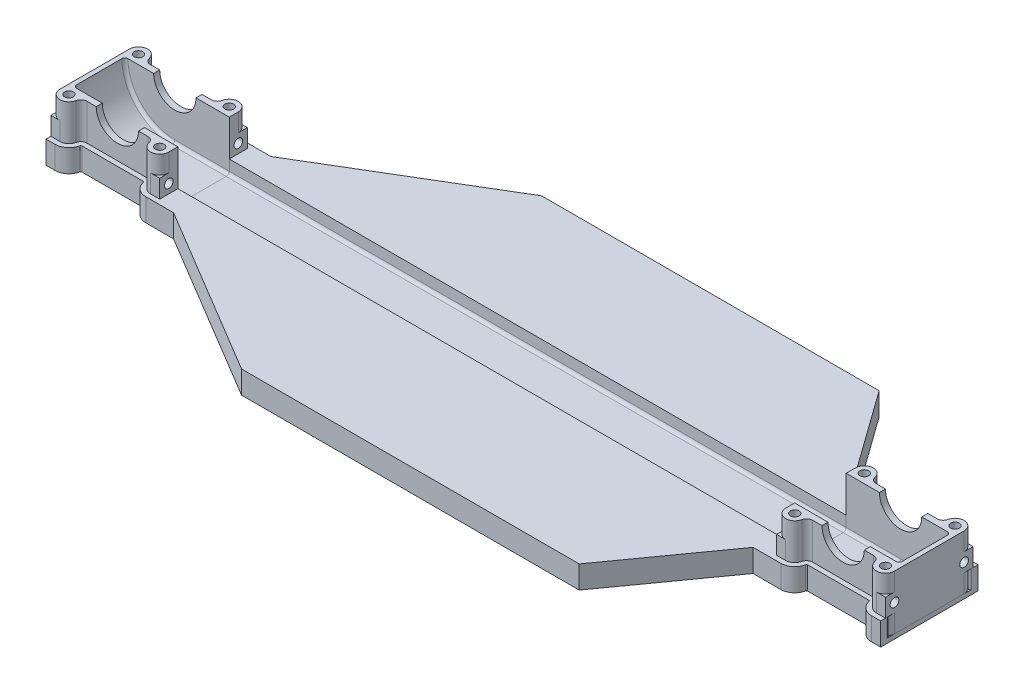
SolidWorks part; units mm, degrees
note: The reader was unsure of these and kept them because the rebuilt part matched: shared geometry of "Sketch1<3>", "Sketch1<4>", "Sketch2<3>", "Sketch3<4>", "Sketch3<5>", "Sketch7<2>", "Sketch7<3>", "Sketch7<4>".
material "6061-T6 (SS)"
ref_plane "Front" through (0, 0, 0) normal (0, 0, 1) x (1, 0, 0)
ref_plane "Top" through (0, 0, 0) normal (0, 1, 0) x (1, 0, 0)
ref_plane "Right" through (0, 0, 0) normal (1, 0, 0) x (0, 0, -1)
sketch "Sketch1" plane through (0, 0, 0) normal (0, 0, 1) x (1, 0, 0)
  line L0 (-28.575, 0) -> (28.575, 0)
  line L1 (-28.575, 0) -> (-28.575, -28.575)
  line L2 (-28.575, -28.575) -> (28.575, -28.575)
  line L3 (28.575, -28.575) -> (28.575, 0)
  line L4 (0, -26.1937) -> (28.575, -26.1937)
  arc A0 (-26.1937, 0) -> (26.1937, 0) centre (0, 0) ccw
  arc A1 (-11.1125, 0) -> (11.1125, 0) centre (0, 0) ccw
  arc A2 (-28.575, 0) -> (28.575, 0) centre (0, 0) ccw
  circle A3 centre (0, 0) radius 28.575 construction
  circle A4 centre (0, 0) radius 26.1937 construction
  dimension "D1" = 52.3875
  dimension "D2" = 22.225
  dimension "D3" = 2.3813
extrude "Boss-Extrude1" add sketch "Sketch1" along normal mid plane 26.9875 contours L0 A2 L4 A0 | A2 L2 L3 L4 | A2 L1 L2
extrude "Boss-Extrude2" add sketch "Sketch1<3>" against normal blind 3.175 from surface contours A2 L1 L2 | L0 A2 L4 A0 | A2 L2 L3 L4 | A2 L4 L3 | L4 A2 L0 A0 | A1 L0 A0
sketch "Sketch1<3>" plane through (0, 0, 0) normal (0, 0, 1) x (1, 0, 0) same geometry as "Sketch1"
extrude "Boss-Extrude3" add sketch "Sketch1<4>" along normal blind 3.175 from surface at 13.4938 contours A2 L1 L2 | L0 A2 L4 A0 | A2 L2 L3 L4 | A2 L4 L3 | L4 A2 L0 A0 | A1 L0 A0 starting at face at (-5.2698, -19.1604, 13.4937)
sketch "Sketch1<4>" plane through (0, 0, 0) normal (0, 0, 1) x (1, 0, 0) same geometry as "Sketch1"
sketch "Sketch2" plane through (0, -28.575, 0) normal (0, -1, 0) x (1, 0, 0)
  line L4 (-28.575, 16.6687) -> (-28.575, -16.6687)
  line L5 (-28.575, 18.2562) -> (-28.575, -18.2563)
  line L6 (-19.05, -18.2563) -> (-19.05, 18.2562)
  line L7 (19.05, 18.2562) -> (19.05, -18.2563)
  line L8 (28.575, -18.2563) -> (28.575, 18.2563)
  line L9 (-28.575, 16.6687) -> (-28.575, -16.6687)
  line L10 (-28.575, -16.6687) -> (28.575, -16.6687)
  line L12 (28.575, 16.6687) -> (-28.575, 16.6687)
  line L16 (28.575, 16.6687) -> (-28.575, 16.6687)
  line L17 (11.1125, -13.4937) -> (-11.1125, -13.4937) construction
  line L18 (-11.1125, 13.4937) -> (11.1125, 13.4937) construction
  line L19 (11.1125, -13.4937) -> (-11.1125, -13.4937)
  line L20 (-11.1125, 13.4937) -> (11.1125, 13.4937)
  line L21 (28.575, -16.6687) -> (28.575, 16.6687)
  line L22 (28.575, -16.6687) -> (28.575, 16.6687)
  line L37 (-28.575, -16.6687) -> (28.575, -16.6687)
  circle A0 centre (-23.8125, 18.2562) radius 4.7625
  circle A1 centre (23.8125, 18.2562) radius 4.7625
  circle A2 centre (-23.8125, -18.2563) radius 4.7625
  circle A3 centre (23.8125, -18.2563) radius 4.7625
  circle A4 centre (-23.8125, 18.2562) radius 2.286
  circle A5 centre (23.8125, 18.2562) radius 2.286
  circle A6 centre (23.8125, -18.2563) radius 2.286
  circle A7 centre (-23.8125, -18.2563) radius 2.286
  line M6 (-28.575, -16.6687) -> (28.575, -16.6687)
  line M8 (28.575, 16.6687) -> (-28.575, 16.6687)
  dimension "D1" = 9.525
  dimension "D5" = 4.572
  dimension "D2" = 0
extrude "Boss-Extrude4" add sketch "Sketch2" against normal up to surface (28.575 mm away) contours A0 L5 M8 | A1 L8 M8 | A3 L8 M6 | A2 L5 M6
fillet "Fillet3" radius 1.5875 4 edges at (-18.5218, -18.5218, -13.4937) (-18.5218, -18.5218, 13.4937) (14.2875, -26.1937, -13.4937) (14.2875, -26.1937, 13.4937)
extrude "Cut-Extrude1" cut sketch "Sketch2<3>" against normal through all both and the other way through all contours A4 | A5 | A6 | A7
sketch "Sketch2<3>" plane through (0, -28.575, 0) normal (0, -1, 0) x (1, 0, 0) same geometry as "Sketch2"
fillet "Fillet7" radius 3.175 4 edges at (19.3224, -14.2875, -16.6687) (-19.3224, -14.2875, -16.6687) (19.3224, -14.2875, 16.6687) (-19.3224, -14.2875, 16.6687)
ref_plane "Plane1" through (190.5, 0, 0) normal (1, 0, 0) x (0, 0, -1)
mirror "Mirror5" about plane through (190.5, 0, 0) normal (1, 0, 0) of bodies 106
sketch "Sketch3" plane through (0, -28.575, 0) normal (0, -1, 0) x (1, 0, 0)
  line L0 (352.425, 18.2563) -> (352.425, -18.2563) construction
  line L1 (364.9646, -16.6687) -> (397.0354, -16.6687) construction
  line L2 (409.575, -18.2563) -> (409.575, 18.2562) construction
  line L3 (397.0354, 16.6687) -> (364.9646, 16.6687) construction
  line L4 (16.0354, 16.6687) -> (-16.0354, 16.6687) construction
  line L5 (-28.575, 18.2562) -> (-28.575, -18.2563) construction
  line L6 (-16.0354, -16.6687) -> (16.0354, -16.6687) construction
  line L7 (28.575, -18.2563) -> (28.575, 18.2563) construction
  line L8 (352.425, 18.2563) -> (352.425, -18.2563)
  line L9 (364.9646, -16.6687) -> (397.0354, -16.6687)
  line L10 (409.575, -18.2563) -> (409.575, 18.2562)
  line L11 (397.0354, 16.6687) -> (364.9646, 16.6687)
  line L12 (16.0354, 16.6687) -> (-16.0354, 16.6687)
  line L13 (-28.575, 18.2562) -> (-28.575, -18.2563)
  line L14 (-16.0354, -16.6687) -> (16.0354, -16.6687)
  line L15 (28.575, -18.2563) -> (28.575, 18.2563)
  line L16 (-24.3902, 22.9836) -> (-24.1024, 23.0188) construction
  line L17 (-24.1024, 23.0188) -> (39.0844, 23.0188) construction
  line L18 (39.0844, 23.0188) -> (127.9844, 76.2) construction
  line L19 (127.9844, 76.2) -> (303.2125, 76.2) construction
  line L20 (303.2125, 76.2) -> (341.3125, 23.0188) construction
  line L21 (341.3125, 23.0188) -> (392.1125, 23.0188) construction
  line L22 (342.6174, -25.5588) -> (394.6083, -25.5588) construction
  line L23 (-28.575, 0) -> (409.575, 0) construction
  line L24 (342.6174, 25.5588) -> (392.2671, 25.5588) construction
  line L25 (157.1625, 15.875) -> (300.0375, 15.875)
  line L26 (157.1625, 15.875) -> (157.1625, 69.85)
  line L27 (157.1625, 69.85) -> (300.0375, 69.85)
  line L28 (300.0375, 15.875) -> (300.0375, 69.85)
  line L29 (157.1625, -15.875) -> (300.0375, -15.875)
  line L30 (157.1625, -15.875) -> (157.1625, -69.85)
  line L31 (157.1625, -69.85) -> (300.0375, -69.85)
  line L32 (300.0375, -15.875) -> (300.0375, -69.85)
  line L33 (341.3125, -23.0188) -> (392.1125, -23.0188) construction
  line L34 (303.2125, -76.2) -> (341.3125, -23.0188) construction
  line L35 (127.9844, -76.2) -> (303.2125, -76.2) construction
  line L36 (39.0844, -23.0188) -> (127.9844, -76.2) construction
  line L37 (-24.1024, -23.0188) -> (39.0844, -23.0188) construction
  line L38 (-24.3902, -22.9836) -> (-24.1024, -23.0188) construction
  line L39 (-24.2571, 25.5588) -> (38.3826, 25.5588) construction
  line L40 (-23.8125, 25.5587) -> (38.3826, 25.5588)
  line L41 (38.3826, 25.5588) -> (127.2826, 78.74)
  line L42 (127.2826, 78.74) -> (304.5174, 78.74)
  line L43 (304.5174, 78.74) -> (342.6174, 25.5588)
  line L44 (342.6174, 25.5588) -> (404.8125, 25.5587)
  line L45 (-24.2571, -25.5588) -> (38.3826, -25.5588) construction
  line L46 (-31.115, 18.2562) -> (-31.115, 25.5588)
  line L47 (-23.8125, -25.5588) -> (38.3826, -25.5588)
  line L48 (38.3826, -25.5588) -> (127.2826, -78.74)
  line L49 (127.2826, -78.74) -> (304.5174, -78.74)
  line L50 (304.5174, -78.74) -> (342.6174, -25.5588)
  line L51 (342.6174, -25.5588) -> (404.8125, -25.5588)
  line L52 (-31.115, 25.5588) -> (-23.8125, 25.5587)
  line L53 (31.115, -18.2563) -> (31.115, 18.2563)
  line L54 (16.0354, 19.2087) -> (-16.0354, 19.2087)
  line L55 (-31.115, 18.2562) -> (-31.115, -18.2563)
  line L56 (-16.0354, -19.2087) -> (16.0354, -19.2087)
  line L57 (349.885, 18.2563) -> (349.885, -18.2563)
  line L58 (364.9646, -19.2087) -> (397.0354, -19.2087)
  line L59 (412.115, -18.2563) -> (412.115, 18.2562)
  line L60 (397.0354, 19.2087) -> (364.9646, 19.2087)
  line L61 (352.425, 13.4937) -> (369.8875, 13.4937) construction
  line L62 (369.8875, -13.4937) -> (352.425, -13.4937) construction
  line L63 (28.575, 13.4937) -> (11.1125, 13.4937) construction
  line L64 (11.1125, -13.4937) -> (28.575, -13.4937) construction
  line L65 (352.425, 13.4937) -> (369.8875, 13.4937)
  line L66 (369.8875, -13.4937) -> (352.425, -13.4937)
  line L67 (28.575, 13.4937) -> (11.1125, 13.4937)
  line L68 (11.1125, -13.4937) -> (28.575, -13.4937)
  line L69 (-31.115, -18.2563) -> (-31.115, -25.5588)
  line L70 (11.1125, 13.4937) -> (369.8875, 13.4937)
  line L71 (11.1125, 13.4937) -> (11.1125, -13.4937)
  line L72 (11.1125, -13.4937) -> (369.8875, -13.4937)
  line L73 (369.8875, 13.4937) -> (369.8875, -13.4937)
  line L74 (392.1125, 23.0188) -> (405.3902, 21.3961) construction
  line L75 (392.1125, -23.0188) -> (392.1166, -22.7857) construction
  line L76 (394.6083, -25.5588) -> (394.6562, -22.8303) construction
  line L77 (392.2671, 25.5588) -> (405.6983, 23.9173) construction
  line L78 (-24.6983, -25.5048) -> (-24.2571, -25.5588) construction
  line L79 (-24.6983, 25.5048) -> (-24.2571, 25.5588) construction
  line L80 (-31.115, -25.5588) -> (-23.8125, -25.5588)
  line L81 (404.8125, 25.5587) -> (412.115, 25.5588)
  line L82 (412.115, 25.5588) -> (412.115, 18.2562)
  line L83 (412.115, -18.2563) -> (412.115, -25.5588)
  line L84 (412.115, -25.5588) -> (404.8125, -25.5588)
  arc A0 (361.8538, 19.2087) -> (352.425, 18.2563) centre (357.1875, 18.2562) ccw construction
  circle A1 centre (404.8125, 18.2562) radius 2.286
  circle A2 centre (404.8125, 18.2562) radius 2.286
  circle A3 centre (357.1875, 18.2562) radius 2.286
  circle A4 centre (357.1875, 18.2562) radius 2.286
  circle A5 centre (357.1875, -18.2563) radius 2.286
  circle A6 centre (357.1875, -18.2563) radius 2.286
  circle A7 centre (404.8125, -18.2563) radius 2.286
  circle A8 centre (404.8125, -18.2563) radius 2.286
  circle A9 centre (-23.8125, 18.2562) radius 2.286
  circle A10 centre (-23.8125, 18.2562) radius 2.286
  circle A11 centre (23.8125, 18.2562) radius 2.286
  circle A12 centre (23.8125, 18.2562) radius 2.286
  circle A13 centre (23.8125, -18.2563) radius 2.286
  circle A14 centre (23.8125, -18.2563) radius 2.286
  circle A15 centre (-23.8125, -18.2563) radius 2.286
  circle A16 centre (-23.8125, -18.2563) radius 2.286
  arc A17 (352.425, -18.2563) -> (361.8538, -19.2088) centre (357.1875, -18.2563) ccw construction
  arc A18 (364.9646, -16.6687) -> (361.8538, -19.2088) centre (364.9646, -19.8438) ccw construction
  arc A19 (400.1462, -19.2088) -> (397.0354, -16.6687) centre (397.0354, -19.8438) ccw construction
  arc A20 (400.1462, -19.2088) -> (409.575, -18.2563) centre (404.8125, -18.2563) ccw construction
  arc A21 (409.575, 18.2562) -> (400.1462, 19.2087) centre (404.8125, 18.2562) ccw construction
  arc A22 (397.0354, 16.6687) -> (400.1462, 19.2087) centre (397.0354, 19.8438) ccw construction
  arc A23 (361.8538, 19.2087) -> (364.9646, 16.6687) centre (364.9646, 19.8438) ccw construction
  arc A24 (28.575, 18.2563) -> (19.1462, 19.2087) centre (23.8125, 18.2562) ccw construction
  arc A25 (16.0354, 16.6687) -> (19.1462, 19.2087) centre (16.0354, 19.8438) ccw construction
  arc A26 (-19.1462, 19.2087) -> (-16.0354, 16.6687) centre (-16.0354, 19.8438) ccw construction
  arc A27 (-19.1462, 19.2087) -> (-28.575, 18.2562) centre (-23.8125, 18.2562) ccw construction
  arc A28 (-28.575, -18.2563) -> (-19.1462, -19.2088) centre (-23.8125, -18.2563) ccw construction
  arc A29 (-16.0354, -16.6687) -> (-19.1462, -19.2088) centre (-16.0354, -19.8438) ccw construction
  arc A30 (19.1462, -19.2088) -> (16.0354, -16.6687) centre (16.0354, -19.8438) ccw construction
  arc A31 (19.1462, -19.2088) -> (28.575, -18.2563) centre (23.8125, -18.2563) ccw construction
  arc A32 (361.8538, 19.2087) -> (352.425, 18.2563) centre (357.1875, 18.2562) ccw
  arc A33 (352.425, -18.2563) -> (361.8538, -19.2088) centre (357.1875, -18.2563) ccw
  arc A34 (364.9646, -16.6687) -> (361.8538, -19.2088) centre (364.9646, -19.8438) ccw
  arc A35 (400.1462, -19.2088) -> (397.0354, -16.6687) centre (397.0354, -19.8438) ccw
  arc A36 (400.1462, -19.2088) -> (409.575, -18.2563) centre (404.8125, -18.2563) ccw
  arc A37 (409.575, 18.2562) -> (400.1462, 19.2087) centre (404.8125, 18.2562) ccw
  arc A38 (397.0354, 16.6687) -> (400.1462, 19.2087) centre (397.0354, 19.8438) ccw
  arc A39 (361.8538, 19.2087) -> (364.9646, 16.6687) centre (364.9646, 19.8438) ccw
  arc A40 (28.575, 18.2563) -> (19.1462, 19.2087) centre (23.8125, 18.2562) ccw
  arc A41 (16.0354, 16.6687) -> (19.1462, 19.2087) centre (16.0354, 19.8438) ccw
  arc A42 (-19.1462, 19.2087) -> (-16.0354, 16.6687) centre (-16.0354, 19.8438) ccw
  arc A43 (-19.1462, 19.2087) -> (-28.575, 18.2562) centre (-23.8125, 18.2562) ccw
  arc A44 (-28.575, -18.2563) -> (-19.1462, -19.2088) centre (-23.8125, -18.2563) ccw
  arc A45 (-16.0354, -16.6687) -> (-19.1462, -19.2088) centre (-16.0354, -19.8438) ccw
  arc A46 (19.1462, -19.2088) -> (16.0354, -16.6687) centre (16.0354, -19.8438) ccw
  arc A47 (19.1462, -19.2088) -> (28.575, -18.2563) centre (23.8125, -18.2563) ccw
  arc A48 (31.115, 18.2563) -> (16.6575, 19.7168) centre (23.8125, 18.2562) ccw
  arc A49 (16.0354, 19.2087) -> (16.6575, 19.7168) centre (16.0354, 19.8437) ccw
  arc A50 (-16.6575, 19.7168) -> (-16.0354, 19.2087) centre (-16.0354, 19.8437) ccw
  arc A51 (-16.6575, 19.7168) -> (-31.115, 18.2562) centre (-23.8125, 18.2562) ccw
  arc A52 (-31.115, -18.2563) -> (-16.6575, -19.7168) centre (-23.8125, -18.2563) ccw
  arc A53 (-16.0354, -19.2087) -> (-16.6575, -19.7168) centre (-16.0354, -19.8438) ccw
  arc A54 (16.6575, -19.7168) -> (16.0354, -19.2087) centre (16.0354, -19.8438) ccw
  arc A55 (16.6575, -19.7168) -> (31.115, -18.2563) centre (23.8125, -18.2563) ccw
  arc A56 (349.885, -18.2563) -> (364.3425, -19.7168) centre (357.1875, -18.2563) ccw
  arc A57 (364.9646, -19.2087) -> (364.3425, -19.7168) centre (364.9646, -19.8438) ccw
  arc A58 (397.6575, -19.7167) -> (397.0354, -19.2087) centre (397.0354, -19.8438) ccw
  arc A59 (397.6575, -19.7167) -> (412.115, -18.2563) centre (404.8125, -18.2563) ccw
  arc A60 (412.115, 18.2562) -> (397.6575, 19.7168) centre (404.8125, 18.2562) ccw
  arc A61 (397.0354, 19.2087) -> (397.6575, 19.7168) centre (397.0354, 19.8437) ccw
  arc A62 (364.3425, 19.7167) -> (364.9646, 19.2087) centre (364.9646, 19.8437) ccw
  arc A63 (364.3425, 19.7167) -> (349.885, 18.2563) centre (357.1875, 18.2562) ccw
  dimension "D9" = 15.875
  dimension "D10" = 15.875
  dimension "D11" = 53.975
  dimension "D12" = 142.875
  dimension "D14" = 12.7
  dimension "D16" = 6.35
  dimension "D18" = 63.5
  dimension "D15" = 38.1
  dimension "D19" = 88.9
  dimension "D17" = 57.15
  dimension "D1" = 0
  dimension "D2" = 0
  dimension "D3" = 0
  dimension "D4" = 0
  dimension "D5" = 0
  dimension "D6" = 0
  dimension "D7" = 0
  dimension "D8" = 0
  dimension "D20" = 2.54
  dimension "D21" = 2.54
  dimension "D22" = 2.54
extrude "Boss-Extrude5" add sketch "Sketch3" along normal blind 2.3813 separate body
extrude "Boss-Extrude6" add sketch "Sketch3<4>" against normal up to surface (2.3813 mm away)
sketch "Sketch3<4>" plane through (0, -28.575, 0) normal (0, -1, 0) x (1, 0, 0) same geometry as "Sketch3"
extrude "Boss-Extrude7" add sketch "Sketch3<5>" against normal blind 9.525
sketch "Sketch3<5>" plane through (0, -28.575, 0) normal (0, -1, 0) x (1, 0, 0) same geometry as "Sketch3"
fillet "Fillet8" radius 1.5875 2 edges at (190.5, -26.1938, -13.4937) (190.5, -26.1938, 13.4937)
sketch "Sketch4" plane through (0, -19.05, 0) normal (0, 1, 0) x (1, 0, 0)
  line L0 (-28.575, -18.2562) -> (-28.575, 18.2563) construction
  line L1 (-19.05, 13.4937) -> (-28.575, 13.4937)
  line L2 (-19.05, 13.4937) -> (-19.05, 23.0188)
  line L3 (-19.05, 23.0188) -> (-28.575, 23.0188)
  line L4 (-28.575, 13.4937) -> (-28.575, 23.0188)
  line L5 (-19.05, 13.4937) -> (-28.575, 23.0188) construction
  line L6 (-19.05, 23.0188) -> (-28.575, 13.4937) construction
  line L7 (352.425, 13.4937) -> (369.8875, 13.4937) construction
  line L8 (19.05, 13.4937) -> (28.575, 13.4937)
  line L9 (19.05, 13.4937) -> (19.05, 23.0188)
  line L10 (19.05, 23.0188) -> (28.575, 23.0188)
  line L11 (28.575, 13.4937) -> (28.575, 23.0188)
  line L12 (19.05, 13.4937) -> (28.575, 23.0188) construction
  line L13 (19.05, 23.0188) -> (28.575, 13.4937) construction
  line L14 (19.05, -13.4937) -> (28.575, -13.4937)
  line L15 (19.05, -13.4937) -> (19.05, -23.0187)
  line L16 (19.05, -23.0187) -> (28.575, -23.0187)
  line L17 (28.575, -13.4937) -> (28.575, -23.0187)
  line L18 (19.05, -13.4937) -> (28.575, -23.0187) construction
  line L19 (19.05, -23.0187) -> (28.575, -13.4937) construction
  line L20 (-28.575, -13.4937) -> (-19.05, -13.4937)
  line L21 (-28.575, -13.4937) -> (-28.575, -23.0188)
  line L22 (-28.575, -23.0188) -> (-19.05, -23.0188)
  line L23 (-19.05, -13.4937) -> (-19.05, -23.0188)
  line L24 (-28.575, -13.4937) -> (-19.05, -23.0188) construction
  line L25 (-28.575, -23.0188) -> (-19.05, -13.4937) construction
  line L26 (400.05, 23.0188) -> (409.575, 23.0188)
  line L27 (400.05, 23.0188) -> (400.05, 13.4938)
  line L28 (400.05, 13.4938) -> (409.575, 13.4938)
  line L29 (409.575, 23.0188) -> (409.575, 13.4938)
  line L30 (400.05, 23.0188) -> (409.575, 13.4938) construction
  line L31 (400.05, 13.4938) -> (409.575, 23.0188) construction
  line L32 (400.05, -13.4937) -> (409.575, -13.4937)
  line L33 (400.05, -13.4937) -> (400.05, -23.0187)
  line L34 (400.05, -23.0187) -> (409.575, -23.0188)
  line L35 (409.575, -13.4937) -> (409.575, -23.0188)
  line L36 (400.05, -13.4937) -> (409.575, -23.0188) construction
  line L37 (400.05, -23.0187) -> (409.575, -13.4937) construction
  line L38 (352.425, -13.4937) -> (361.95, -13.4938)
  line L39 (352.425, -13.4937) -> (352.425, -23.0187)
  line L40 (352.425, -23.0187) -> (361.95, -23.0187)
  line L41 (361.95, -13.4938) -> (361.95, -23.0187)
  line L42 (352.425, -13.4937) -> (361.95, -23.0187) construction
  line L43 (352.425, -23.0187) -> (361.95, -13.4938) construction
  line L44 (352.425, 13.4937) -> (361.95, 13.4937)
  line L45 (352.425, 13.4937) -> (352.425, 23.0188)
  line L46 (352.425, 23.0188) -> (361.95, 23.0188)
  line L47 (361.95, 13.4937) -> (361.95, 23.0188)
  line L48 (352.425, 13.4937) -> (361.95, 23.0188) construction
  line L49 (352.425, 23.0188) -> (361.95, 13.4937) construction
  line L50 (369.8875, 13.4937) -> (369.8875, 16.6687) construction
  line L51 (369.8875, 16.6687) -> (364.9646, 16.6687) construction
  line L52 (352.425, 18.2563) -> (352.425, 13.4937) construction
  line L53 (364.9646, -16.6687) -> (369.8875, -16.6687) construction
  line L54 (369.8875, -16.6687) -> (369.8875, -13.4937) construction
  line L55 (369.8875, -13.4937) -> (352.425, -13.4937) construction
  line L56 (352.425, -13.4937) -> (352.425, -18.2563) construction
  line L57 (409.575, -18.2562) -> (409.575, 18.2563) construction
  line L58 (397.0354, 16.6687) -> (392.1125, 16.6687) construction
  line L59 (392.1125, 16.6687) -> (392.1125, 13.4937) construction
  line L60 (392.1125, 13.4937) -> (405.6062, 13.4937) construction
  line L61 (407.1938, 11.9062) -> (407.1938, -11.9062) construction
  line L62 (405.6062, -13.4937) -> (392.1125, -13.4937) construction
  line L63 (392.1125, -13.4937) -> (392.1125, -16.6687) construction
  line L64 (392.1125, -16.6687) -> (397.0354, -16.6687) construction
  line L65 (11.1125, -16.6687) -> (16.0354, -16.6687) construction
  line L66 (28.575, -18.2563) -> (28.575, -13.4937) construction
  line L67 (28.575, -13.4937) -> (11.1125, -13.4937) construction
  line L68 (11.1125, -13.4937) -> (11.1125, -16.6687) construction
  line L69 (11.1125, 13.4937) -> (28.575, 13.4937) construction
  line L70 (28.575, 13.4937) -> (28.575, 18.2563) construction
  line L71 (16.0354, 16.6687) -> (11.1125, 16.6687) construction
  line L72 (11.1125, 16.6687) -> (11.1125, 13.4937) construction
  line L73 (-28.575, 18.2563) -> (-28.575, -18.2562) construction
  line L74 (-16.0354, -16.6687) -> (-11.1125, -16.6687) construction
  line L75 (-11.1125, -16.6687) -> (-11.1125, -13.4937) construction
  line L76 (-11.1125, -13.4937) -> (-24.6062, -13.4937) construction
  line L77 (-26.1937, -11.9062) -> (-26.1937, 11.9062) construction
  line L78 (-24.6062, 13.4937) -> (-11.1125, 13.4937) construction
  line L79 (-11.1125, 13.4937) -> (-11.1125, 16.6687) construction
  line L80 (-11.1125, 16.6687) -> (-16.0354, 16.6687) construction
  line L81 (352.425, 13.4937) -> (369.8875, 13.4937)
  line L82 (369.8875, 13.4937) -> (369.8875, 16.6687)
  line L83 (369.8875, 16.6687) -> (364.9646, 16.6687)
  line L84 (352.425, 18.2563) -> (352.425, 13.4937)
  line L85 (364.9646, -16.6687) -> (369.8875, -16.6687)
  line L86 (369.8875, -16.6687) -> (369.8875, -13.4937)
  line L87 (369.8875, -13.4937) -> (352.425, -13.4937)
  line L88 (352.425, -13.4937) -> (352.425, -18.2563)
  line L89 (409.575, -18.2562) -> (409.575, 18.2563)
  line L90 (397.0354, 16.6687) -> (392.1125, 16.6687)
  line L91 (392.1125, 16.6687) -> (392.1125, 13.4937)
  line L92 (392.1125, 13.4937) -> (405.6062, 13.4937)
  line L93 (407.1938, 11.9062) -> (407.1938, -11.9062)
  line L94 (405.6062, -13.4937) -> (392.1125, -13.4937)
  line L95 (392.1125, -13.4937) -> (392.1125, -16.6687)
  line L96 (392.1125, -16.6687) -> (397.0354, -16.6687)
  line L97 (11.1125, -16.6687) -> (16.0354, -16.6687)
  line L98 (28.575, -18.2563) -> (28.575, -13.4937)
  line L99 (28.575, -13.4937) -> (11.1125, -13.4937)
  line L100 (11.1125, -13.4937) -> (11.1125, -16.6687)
  line L101 (11.1125, 13.4937) -> (28.575, 13.4937)
  line L102 (28.575, 13.4937) -> (28.575, 18.2563)
  line L103 (16.0354, 16.6687) -> (11.1125, 16.6687)
  line L104 (11.1125, 16.6687) -> (11.1125, 13.4937)
  line L105 (-28.575, 18.2563) -> (-28.575, -18.2562)
  line L106 (-16.0354, -16.6687) -> (-11.1125, -16.6687)
  line L107 (-11.1125, -16.6687) -> (-11.1125, -13.4937)
  line L108 (-11.1125, -13.4937) -> (-24.6062, -13.4937)
  line L109 (-26.1937, -11.9062) -> (-26.1937, 11.9062)
  line L110 (-24.6062, 13.4937) -> (-11.1125, 13.4937)
  line L111 (-11.1125, 13.4937) -> (-11.1125, 16.6687)
  line L112 (-11.1125, 16.6687) -> (-16.0354, 16.6687)
  circle A0 centre (404.8125, 18.2563) radius 2.286 construction
  circle A1 centre (404.8125, -18.2562) radius 2.286 construction
  circle A2 centre (357.1875, -18.2562) radius 2.286 construction
  circle A3 centre (357.1875, 18.2563) radius 2.286 construction
  circle A4 centre (-23.8125, 18.2563) radius 2.286 construction
  circle A5 centre (23.8125, 18.2563) radius 2.286 construction
  circle A6 centre (23.8125, -18.2562) radius 2.286 construction
  circle A7 centre (-23.8125, -18.2562) radius 2.286 construction
  circle A8 centre (404.8125, 18.2563) radius 2.286
  circle A9 centre (404.8125, -18.2562) radius 2.286
  circle A10 centre (357.1875, -18.2562) radius 2.286
  circle A11 centre (357.1875, 18.2563) radius 2.286
  circle A12 centre (-23.8125, 18.2563) radius 2.286
  circle A13 centre (23.8125, 18.2563) radius 2.286
  circle A14 centre (23.8125, -18.2562) radius 2.286
  circle A15 centre (-23.8125, -18.2562) radius 2.286
  arc A16 (361.8538, 19.2088) -> (364.9646, 16.6687) centre (364.9646, 19.8438) ccw construction
  arc A17 (361.8538, 19.2088) -> (352.425, 18.2563) centre (357.1875, 18.2563) ccw construction
  arc A18 (352.425, -18.2563) -> (361.8538, -19.2087) centre (357.1875, -18.2562) ccw construction
  arc A19 (364.9646, -16.6687) -> (361.8538, -19.2087) centre (364.9646, -19.8438) ccw construction
  arc A20 (409.575, 18.2563) -> (400.1462, 19.2088) centre (404.8125, 18.2563) ccw construction
  arc A21 (397.0354, 16.6687) -> (400.1462, 19.2088) centre (397.0354, 19.8438) ccw construction
  arc A22 (407.1938, 11.9062) -> (405.6062, 13.4937) centre (405.6062, 11.9062) ccw construction
  arc A23 (405.6062, -13.4937) -> (407.1938, -11.9062) centre (405.6062, -11.9062) ccw construction
  arc A24 (400.1462, -19.2087) -> (397.0354, -16.6687) centre (397.0354, -19.8438) ccw construction
  arc A25 (400.1462, -19.2087) -> (409.575, -18.2562) centre (404.8125, -18.2562) ccw construction
  arc A26 (19.1462, -19.2087) -> (16.0354, -16.6687) centre (16.0354, -19.8438) ccw construction
  arc A27 (19.1462, -19.2087) -> (28.575, -18.2563) centre (23.8125, -18.2562) ccw construction
  arc A28 (28.575, 18.2563) -> (19.1462, 19.2088) centre (23.8125, 18.2563) ccw construction
  arc A29 (16.0354, 16.6687) -> (19.1462, 19.2088) centre (16.0354, 19.8438) ccw construction
  arc A30 (-28.575, -18.2562) -> (-19.1462, -19.2087) centre (-23.8125, -18.2562) ccw construction
  arc A31 (-16.0354, -16.6687) -> (-19.1462, -19.2087) centre (-16.0354, -19.8438) ccw construction
  arc A32 (-26.1937, -11.9062) -> (-24.6062, -13.4937) centre (-24.6062, -11.9062) ccw construction
  arc A33 (-24.6062, 13.4937) -> (-26.1937, 11.9062) centre (-24.6062, 11.9062) ccw construction
  arc A34 (-19.1462, 19.2088) -> (-16.0354, 16.6687) centre (-16.0354, 19.8438) ccw construction
  arc A35 (-19.1462, 19.2088) -> (-28.575, 18.2563) centre (-23.8125, 18.2563) ccw construction
  arc A36 (361.8538, 19.2088) -> (364.9646, 16.6687) centre (364.9646, 19.8438) ccw
  arc A37 (361.8538, 19.2088) -> (352.425, 18.2563) centre (357.1875, 18.2563) ccw
  arc A38 (352.425, -18.2563) -> (361.8538, -19.2087) centre (357.1875, -18.2562) ccw
  arc A39 (364.9646, -16.6687) -> (361.8538, -19.2087) centre (364.9646, -19.8438) ccw
  arc A40 (409.575, 18.2563) -> (400.1462, 19.2088) centre (404.8125, 18.2563) ccw
  arc A41 (397.0354, 16.6687) -> (400.1462, 19.2088) centre (397.0354, 19.8438) ccw
  arc A42 (407.1938, 11.9062) -> (405.6062, 13.4937) centre (405.6062, 11.9062) ccw
  arc A43 (405.6062, -13.4937) -> (407.1938, -11.9062) centre (405.6062, -11.9062) ccw
  arc A44 (400.1462, -19.2087) -> (397.0354, -16.6687) centre (397.0354, -19.8438) ccw
  arc A45 (400.1462, -19.2087) -> (409.575, -18.2562) centre (404.8125, -18.2562) ccw
  arc A46 (19.1462, -19.2087) -> (16.0354, -16.6687) centre (16.0354, -19.8438) ccw
  arc A47 (19.1462, -19.2087) -> (28.575, -18.2563) centre (23.8125, -18.2562) ccw
  arc A48 (28.575, 18.2563) -> (19.1462, 19.2088) centre (23.8125, 18.2563) ccw
  arc A49 (16.0354, 16.6687) -> (19.1462, 19.2088) centre (16.0354, 19.8438) ccw
  arc A50 (-28.575, -18.2562) -> (-19.1462, -19.2087) centre (-23.8125, -18.2562) ccw
  arc A51 (-16.0354, -16.6687) -> (-19.1462, -19.2087) centre (-16.0354, -19.8438) ccw
  arc A52 (-26.1937, -11.9062) -> (-24.6062, -13.4937) centre (-24.6062, -11.9062) ccw
  arc A53 (-24.6062, 13.4937) -> (-26.1937, 11.9062) centre (-24.6062, 11.9062) ccw
  arc A54 (-19.1462, 19.2088) -> (-16.0354, 16.6687) centre (-16.0354, 19.8438) ccw
  arc A55 (-19.1462, 19.2088) -> (-28.575, 18.2563) centre (-23.8125, 18.2563) ccw
extrude "Boss-Extrude8" add sketch "Sketch4" along normal blind 9.525 contours A45 L34 L35 | A40 L29 L26 | A37 L46 L45 | A38 L39 L40 | A48 L11 L10 | A47 L16 L17 | A55 L3 L4 | A50 L21 L22 | A9 | A8 | A11 | A10 | A14 | A13 | A12 | A15
sketch "Sketch7" plane through (-28.575, 0, 0) normal (-1, 0, 0) x (0, 0, 1)
  line L0 (-23.0188, -9.525) -> (-23.0188, -19.05) construction
  line L1 (-18.2563, -9.525) -> (-23.0188, -9.525) construction
  line L2 (23.0188, -9.525) -> (23.0188, -19.05) construction
  circle A0 centre (-18.2563, -14.2875) radius 2.286
  circle A1 centre (18.2563, -14.2875) radius 2.286
  dimension "D1" = 4.572
  dimension "D2" = 4.7625
  dimension "D3" = 4.7625
  dimension "D4" = 4.7625
extrude "Cut-Extrude7" cut sketch "Sketch7" against normal blind 7.9375
extrude "Cut-Extrude8" cut sketch "Sketch7<2>" against normal blind 7.9375 from surface at -388.9375
sketch "Sketch7<2>" plane through (-28.575, 0, 0) normal (-1, 0, 0) x (0, 0, 1) same geometry as "Sketch7"
extrude "Cut-Extrude9" cut sketch "Sketch7<3>" along normal blind 7.9375 from surface at -57.15 starting at face at (28.575, -15.206, 0)
sketch "Sketch7<3>" plane through (-28.575, 0, 0) normal (-1, 0, 0) x (0, 0, 1) same geometry as "Sketch7"
extrude "Cut-Extrude10" cut sketch "Sketch7<4>" along normal blind 7.9375 from surface at -430.2125
sketch "Sketch7<4>" plane through (-28.575, 0, 0) normal (-1, 0, 0) x (0, 0, 1) same geometry as "Sketch7"
sketch "Sketch8" plane through (0, -30.9563, 0) normal (0, -1, 0) x (1, 0, 0)
  line L0 (409.575, -18.2563) -> (409.575, 18.2562) construction
  line L1 (-58.164, 49.9909) -> (-28.575, 49.9909)
  line L2 (-58.164, 49.9909) -> (-58.164, -40.831)
  line L3 (-58.164, -40.831) -> (-28.575, -40.831)
  line L4 (-28.575, 49.9909) -> (-28.575, -40.831)
  line L5 (481.3549, 84.3026) -> (409.575, 84.3026)
  line L6 (481.3549, 84.3026) -> (481.3549, -155.5074)
  line L7 (481.3549, -155.5074) -> (409.575, -155.5074)
  line L8 (409.575, 84.3026) -> (409.575, -155.5074)
  line L9 (-28.575, 18.2562) -> (-28.575, -18.2563) construction
  line L10 (409.575, -18.2563) -> (409.575, 18.2562)
  line L11 (-28.575, 18.2562) -> (-28.575, -18.2563)
  line M16 (404.8125, -25.5588) -> (412.115, -25.5588)
  line M17 (412.115, -25.5588) -> (412.115, 25.5588)
  line M18 (412.115, 25.5588) -> (404.8125, 25.5587)
  line M34 (-23.8125, 25.5587) -> (-31.115, 25.5588)
  line M35 (-31.115, 25.5588) -> (-31.115, -25.5588)
  line M36 (-31.115, -25.5588) -> (-23.8125, -25.5588)
extrude "Cut-Extrude11" cut sketch "Sketch8" against normal through all both and the other way through all contours L4 M34 M35 M36 | L8 M18 M16 M17
fillet "Fillet10" radius 0.7937 4 edges at (-28.575, -23.8125, 18.2562) (-28.575, -23.8125, -18.2563) (409.575, -23.8125, -18.2563) (409.575, -23.8125, 18.2562)
equation "\"D10@Sketch3\"=\"D9@Sketch3\""
